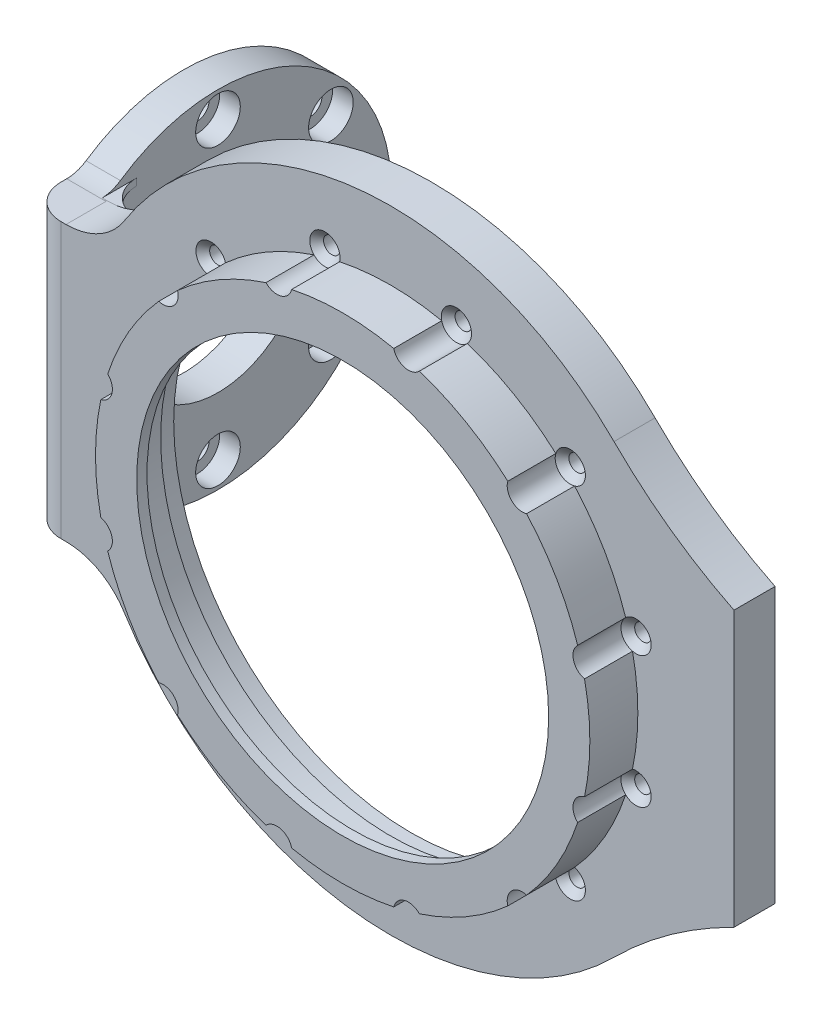
SolidWorks part; units mm, degrees
ref_plane "前视基准面" through (0, 0, 0) normal (0, 0, 1) x (1, 0, 0)
ref_plane "上视基准面" through (0, 0, 0) normal (0, 1, 0) x (1, 0, 0)
ref_plane "右视基准面" through (0, 0, 0) normal (1, 0, 0) x (0, 0, -1)
sketch "草图3" plane through (0, 0, 0) normal (0, 0, 1) x (1, 0, 0)
  circle A0 centre (0, 0) radius 34.6
  circle A1 centre (0, 0) radius 46
extrude "凸台-拉伸2" add sketch "草图3" along normal blind 3
ref_plane "基准面5" through (0, 0, 3) normal (0, 0, 1) x (1, 0, 0)
sketch "草图5" plane through (0, 0, 3) normal (0, 0, 1) x (1, 0, 0)
  circle A0 centre (0, 0) radius 33.5
  circle A1 centre (0, 0) radius 36
extrude "凸台-拉伸3" add sketch "草图5" along normal blind 5.49
sketch "草图2" plane through (0, 0, 0) normal (0, 0, 1) x (1, 0, 0)
  circle A0 centre (0, 0) radius 41.6
  circle A1 centre (0, 0) radius 46
extrude "凸台-拉伸1" add sketch "草图2" against normal blind 2.98
sketch "草图6" plane through (0, 0, 8.49) normal (0, 0, 1) x (1, 0, 0)
  circle A0 centre (0, 0) radius 30
  circle A1 centre (0, 0) radius 36
extrude "凸台-拉伸4" add sketch "草图6" along normal blind 1.5
sketch "草图8" plane through (0, 0, 0) normal (0, 0, 1) x (1, 0, 0)
  line L1 (-50, -20) -> (-50, 20)
  line L3 (50, -20) -> (50, 20)
  line L4 (-50, 20) -> (-41.4246, 20)
  line L5 (-50, -20) -> (-41.4246, -20)
  arc A5 (32.5269, 32.5269) -> (32.5269, -32.5269) centre (0, 0) cw
  arc A6 (50, -20) -> (32.5269, -32.5269) centre (79.2531, -79.2531) ccw
  arc A7 (50, 20) -> (32.5269, 32.5269) centre (79.2531, 79.2531) cw
  circle A8 centre (0, 0) radius 46 construction
  arc A9 (-41.4246, -20) -> (-41.4246, 20) centre (0, 0) cw
extrude "凸台-拉伸5" add sketch "草图8" along normal blind 3 and the other way blind 2.98
hole_wizard "M2 锥坑平头的锥孔1" positions "3D草图3" profile "草图12" countersink size "M2" standard "BSI" end condition through all
sketch3d "3D草图3"
  line L2 (0, 0, 0) -> (0, 37, 0)
  line L3 (0, 0, 0) -> (11.5811, 0, 0)
  point P55 (9.5763, 35.7393, 3)
  point P76 (26.163, 26.163, 3)
  point P83 (35.7393, 9.5763, 3)
  point P96 (-35.7393, 9.5763, 3)
  point P97 (-26.163, 26.163, 3)
  point P98 (-9.5763, 35.7393, 3)
  point P99 (35.7393, -9.5763, 3)
  point P100 (26.163, -26.163, 3)
  point P101 (9.5763, -35.7393, 3)
  point P102 (-9.5763, -35.7393, 3)
  point P103 (-26.163, -26.163, 3)
  point P104 (-35.7393, -9.5763, 3)
sketch "草图12" plane through (-35.7393, -9.5763, 3) normal (1, 0, 0) x (0, -1, 0)
  line L0 (0, 0) -> (0, 5.98)
  line L1 (0, 5.98) -> (1.2, 5.98)
  line L2 (1.2, 5.98) -> (1.2, 1)
  line L3 (1.2, 1) -> (2.2, 0)
  line L5 (2.2, 0) -> (0, 0)
  line L6 (-1.2, 1) -> (-2.2, 0) construction
  line L11 (0, -6.35) -> (0, 107.95) construction
  dimension "通孔孔直径" = 2.4
  dimension "通孔孔深度" = 5.98
  dimension "近端锥形沉头孔直径" = 4.4
  dimension "近端锥形沉头孔角度" = 90
sketch "草图13" plane through (0, 0, 3) normal (0, 0, 1) x (1, 0, 0)
  line L0 (0, 0) -> (0, 10.9464)
  line L1 (0, 0) -> (8.3109, 0)
  circle A0 centre (-35.7393, 9.5763) radius 2.2
  circle A1 centre (-26.163, 26.163) radius 2.2
  circle A2 centre (-9.5763, 35.7393) radius 2.2
  circle A3 centre (-9.5763, -35.7393) radius 2.2
  circle A4 centre (-26.163, -26.163) radius 2.2
  circle A5 centre (-35.7393, -9.5763) radius 2.2
  circle A6 centre (9.5763, -35.7393) radius 2.2
  circle A7 centre (26.163, -26.163) radius 2.2
  circle A8 centre (9.5763, 35.7393) radius 2.2
  circle A9 centre (26.163, 26.163) radius 2.2
  circle A10 centre (35.7393, -9.5763) radius 2.2
  circle A11 centre (35.7393, 9.5763) radius 2.2
extrude "切除-拉伸1" cut sketch "草图13" along normal up to next contours A5 | A4 | A0 | A1 | A2 | A9 | A11 | A10 | A6 | A3 | A8 | A7 region at (-35.7393, 9.5763, 3) region at (-26.163, 26.163, 3) region at (-9.5763, 35.7393, 3) region at (-9.5763, -35.7393, 3) region at (-26.163, -26.163, 3) region at (-35.7393, -9.5763, 3) region at (9.5763, -35.7393, 3) region at (26.163, 26.163, 3) region at (35.7393, -9.5763, 3) region at (35.7393, 9.5763, 3)
ref_plane "基准面6" through (-50, 0, 0) normal (-1, 0, 0) x (0, 0, 1)
sketch "草图14" plane through (-50, 0, 0) normal (-1, 0, 0) x (0, 0, 1)
  line L0 (-4.4369, 20) -> (3, 20)
  line L3 (3, 20) -> (3, -20)
  line L5 (-4.4369, -20) -> (3, -20)
  arc A1 (-4.4369, -20) -> (-4.4369, 20) centre (-19.85, 0) cw
  point P0 (0, 0)
extrude "凸台-拉伸6" add sketch "草图14" along normal blind 3 and the other way blind 2
fillet "圆角1" radius 10 1 edges at (-41.4246, 20, 0.01)
fillet "圆角2" radius 10 1 edges at (-41.4246, -20, 0.01)
fillet "圆角3" radius 5 1 edges at (-50.5, 20, -4.4369)
fillet "圆角4" radius 5 1 edges at (-53, 0, 3)
fillet "圆角5" radius 5 1 edges at (-50.5, -20, -4.4369)
ref_plane "基准面7" through (-48, -20.0026, -2.98) normal (0, 1, 0) x (1, 0, 0)
sketch "草图17" plane through (-48, -20.0026, -2.98) normal (0, 1, 0) x (1, 0, 0)
  line L0 (0, 0) -> (0, 5)
  line L1 (0, 2.6539) -> (0, 42.12) construction
  line L2 (0, 0) -> (5, 0)
  line L3 (9.1576, 0) -> (0.4856, 0) construction
  arc A1 (0, 5) -> (5, 0) centre (5, 5) ccw
extrude "凸台-拉伸7" add sketch "草图17" along normal blind 1
pattern_linear "阵列(线性)1" count 8 spacing 5.5722 along (0, 1, 0) skipping (1, 0), (6, 0) of "凸台-拉伸7"
sketch "草图18" plane through (0, 0, 3) normal (0, 0, 1) x (1, 0, 0)
  circle A0 centre (0, 0) radius 46
extrude "切除-拉伸2" cut sketch "草图18" against normal blind 2 from surface starting at face at (41.6, 0, -2.98)
sketch "草图19" plane through (-50, 0, 0) normal (-1, 0, 0) x (0, 0, 1)
  circle A1 centre (-19.85, 0) radius 13
extrude "切除-拉伸3" cut sketch "草图19" against normal through all and the other way through all contours A1
hole_wizard "M3 六角凹头盖的柱孔1" positions "3D草图4" profile "草图20" counterbore size "M3" standard "BSI" end condition up to next
sketch3d "3D草图4"
  point P0 (-48, 21.4664, -19.85)
  point P42 (-48, 13.7984, -36.2942)
  point P61 (-48, 13.7984, -3.4058)
  point P72 (-48, -13.7984, -36.2942)
  point P74 (-48, -21.4664, -19.85)
  point P76 (-48, -13.7984, -3.4058)
  point P79 (0, 0, 0)
  point P80 (0, 0, 0)
  point P81 (0, 0, 0)
  point P82 (0, 0, 0)
  point P83 (0, 0, 0)
  point P84 (0, 0, 0)
  point P85 (0, 0, 0)
  point P86 (0, 0, 0)
  point P87 (0, 0, 0)
  point P88 (0, 0, 0)
  point P89 (0, 0, 0)
  point P90 (0, 0, 0)
  point P91 (0, 0, 0)
sketch "草图20" plane through (-48, 21.4664, -19.85) normal (0, 1, 0) x (0, 0, -1)
  line L0 (0, 0) -> (0, 5)
  line L1 (0, 5) -> (1.7, 5)
  line L3 (1.7, 5) -> (1.7, 3)
  line L4 (1.7, 3) -> (3.25, 3)
  line L5 (3.25, 3) -> (3.25, 0)
  line L7 (3.25, 0) -> (0, 0)
  line L11 (0, -6.35) -> (0, 107.95) construction
  dimension "通孔孔直径" = 3.4
  dimension "通孔孔深度" = 5
  dimension "柱形沉头孔直径" = 6.5
  dimension "柱形沉头孔深度" = 3
sketch "草图21" plane through (-50, 0, 0) normal (-1, 0, 0) x (0, 0, 1)
  circle A0 centre (-3.4058, 13.7984) radius 3
extrude "切除-拉伸4" cut sketch "草图21" against normal blind 15
